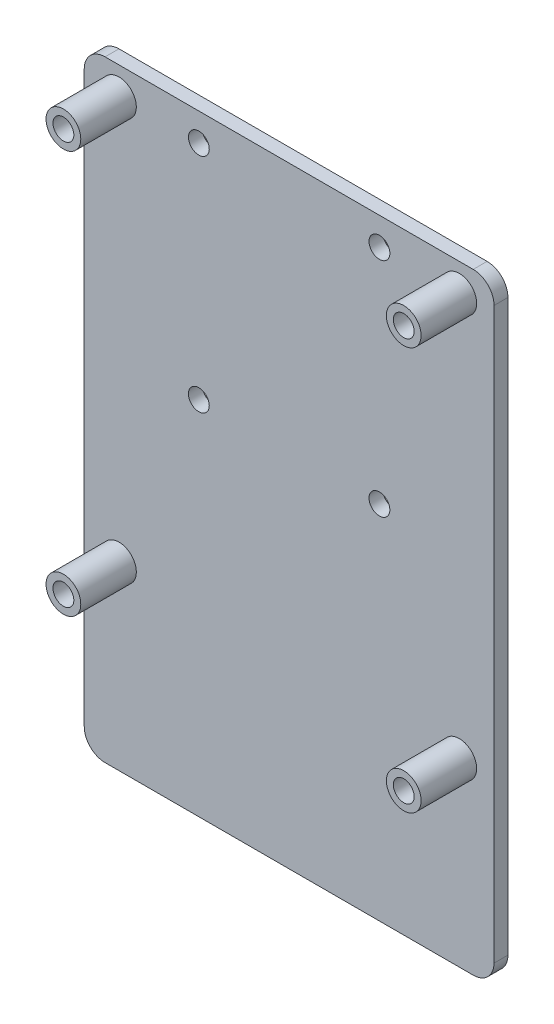
SolidWorks part; units mm, degrees
ref_plane "前视基准面" through (0, 0, 0) normal (0, 0, 1) x (1, 0, 0)
ref_plane "上视基准面" through (0, 0, 0) normal (0, 1, 0) x (1, 0, 0)
ref_plane "右视基准面" through (0, 0, 0) normal (1, 0, 0) x (0, 0, -1)
other "Configuration Table"
sketch "Sketch1" plane through (0, 0, 0) normal (0, 0, 1) x (1, 0, 0)
  line L5 (-13, 16) -> (13, 16)
  line L6 (-13, 16) -> (-13, -16)
  line L7 (-13, -16) -> (13, -16)
  line L8 (13, 16) -> (13, -16)
  line L9 (0, -16) -> (0, 16) construction
  line L10 (-13, 0) -> (13, 0) construction
  line L11 (-24.5, 16) -> (24.5, 16)
  line L12 (-24.5, 16) -> (-24.5, -42)
  line L13 (-24.5, -42) -> (24.5, -42)
  line L14 (24.5, 16) -> (24.5, -42)
  line L15 (-29.5, 20) -> (29.5, 20)
  line L16 (-29.5, 20) -> (-29.5, -68)
  line L17 (-29.5, -68) -> (29.5, -68)
  line L18 (29.5, 20) -> (29.5, -68)
  circle A0 centre (-13, 16) radius 1.5
  circle A1 centre (13, 16) radius 1.5
  circle A2 centre (13, -16) radius 1.5
  circle A3 centre (-13, -16) radius 1.5
  circle A4 centre (-24.5, 16) radius 1.5
  circle A5 centre (24.5, 16) radius 1.5
  circle A6 centre (24.5, -42) radius 1.5
  circle A7 centre (-24.5, -42) radius 1.5
  circle A9 centre (-24.5, 16) radius 2.5
  circle A10 centre (24.5, 16) radius 2.5
  circle A11 centre (24.5, -42) radius 2.5
  circle A12 centre (-24.5, -42) radius 2.5
  point P0 (0, 0)
  dimension "D1" = 32
  dimension "D2" = 26
  dimension "D3" = 58
  dimension "D4" = 49
  dimension "D5" = 24.5
  dimension "D6" = 88
  dimension "D7" = 59
  dimension "D8" = 29.5
  dimension "D9" = 4
extrude "Boss-Extrude1" add sketch "Sketch1" along normal blind 2 contours A12 L13 A11 L14 A10 L11 A1 L8 A2 L7 A3 L6 A0 A9 L12 | A3 L7 A2 L8 A1 L11 A0 L6 | L18 L15 L16 L17 A12 L12 A9 L11 A0 A1 A10 L14 A11 L13 region at (0, 0, 0) region at (0, -18.5065, 0) region at (0, 18.9405, 0)
extrude "Boss-Extrude2" add sketch "Sketch1<3>" along normal blind 10 contours L11 A9 L12 A4 | L12 A9 L11 A4 | L14 A10 L11 A5 | L11 A10 L14 A5 | L13 A12 L12 A7 | L12 A12 L13 A7 | L13 A11 L14 A6 | L14 A11 L13 A6 region at (-23.2002, 14.7002, 0) region at (-22.5, 16.0707, 0) region at (24.5, 18.4293, 0) region at (23.2002, 14.7002, 0) region at (-23.2002, -40.7002, 0) region at (-24.5707, -40, 0) region at (26.2178, -40.2822, 0) region at (23.2002, -40.7002, 0)
sketch "Sketch1<3>" plane through (0, 0, 0) normal (0, 0, 1) x (1, 0, 0) same geometry as "Sketch1"
fillet "Fillet1" radius 3 4 edges at (29.5, 20, 1) (-29.5, 20, 1) (29.5, -68, 1) (-29.5, -68, 1)
